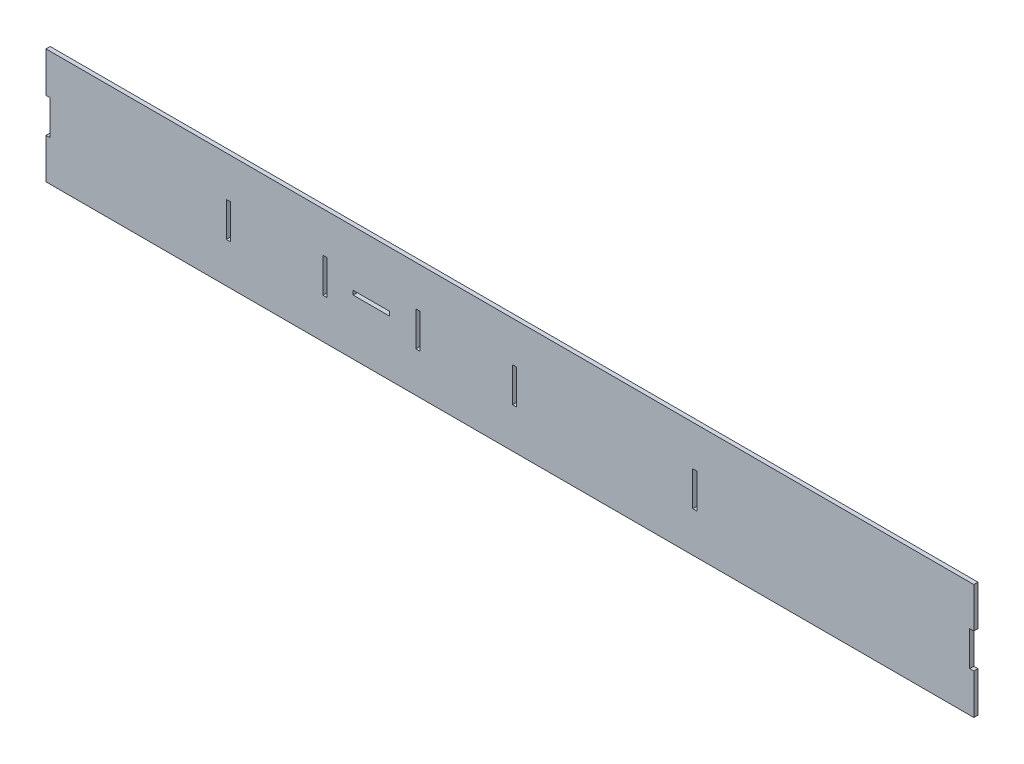
SolidWorks part; units mm, degrees
ref_plane "Front Plane" through (0, 0, 0) normal (0, 0, 1) x (1, 0, 0)
ref_plane "Top Plane" through (0, 0, 0) normal (0, 1, 0) x (1, 0, 0)
ref_plane "Right Plane" through (0, 0, 0) normal (1, 0, 0) x (0, 0, -1)
sketch "Sketch1" plane through (0, 0, 0) normal (0, 0, 1) x (1, 0, 0)
  line L0 (-1.524, -7.869) -> (0, -7.869)
  line L1 (-1.524, -22.6446) -> (338.8496, -22.6446)
  line L2 (-1.524, -22.6446) -> (-1.524, -7.869)
  line L3 (-1.524, 19.6067) -> (338.8496, 19.6067)
  line L4 (338.8496, -22.6446) -> (338.8496, 19.6067)
  line L5 (0, -7.869) -> (0, 4.831)
  line L6 (0, 4.831) -> (-1.524, 4.831)
  line L7 (-1.524, 4.831) -> (-1.524, 19.6067)
  line L9 (101.6, 4.831) -> (100.076, 4.831)
  line L10 (101.6, 4.831) -> (101.6, -7.869)
  line L11 (101.6, -7.869) -> (100.076, -7.869)
  line L12 (100.076, 4.831) -> (100.076, -7.869)
  line L13 (134.1256, -7.869) -> (135.6496, -7.869)
  line L14 (134.1256, -7.869) -> (134.1256, 4.831)
  line L15 (134.1256, 4.831) -> (135.6496, 4.831)
  line L16 (135.6496, -7.869) -> (135.6496, 4.831)
  line L17 (235.7256, -7.869) -> (237.2496, -7.869)
  line L18 (235.7256, -7.869) -> (235.7256, 4.831)
  line L19 (235.7256, 4.831) -> (237.2496, 4.831)
  line L20 (237.2496, -7.869) -> (237.2496, 4.831)
  line L21 (338.8496, -7.869) -> (337.3256, -7.869)
  line L22 (338.8496, -7.869) -> (338.8496, 4.831)
  line L23 (338.8496, 4.831) -> (337.3256, 4.831)
  line L24 (337.3256, -7.869) -> (337.3256, 4.831)
extrude "Boss-Extrude1" add sketch "Sketch1" along normal blind 1.524 contours L21 L24 L23 L4 L3 L7 L6 L5 L0 L2 L1 L12 L9 L10 L11 L16 L13 L14 L15 L20 L17 L18 L19 region at (168.7086, -1.519, 0)
sketch "Sketch2" plane through (0, 0, 1.524) normal (0, 0, 1) x (1, 0, 0)
  line L0 (101.6, -1.519) -> (134.1256, -1.519) construction
  line L1 (66.1281, -7.869) -> (64.6041, -7.869)
  line L2 (66.1281, -7.869) -> (66.1281, 4.831)
  line L3 (66.1281, 4.831) -> (64.6041, 4.831)
  line L4 (64.6041, -7.869) -> (64.6041, 4.831)
  line L5 (101.6, 4.831) -> (101.6, -7.869) construction
  line L6 (134.1256, -7.869) -> (134.1256, 4.831) construction
  line L7 (117.8628, -1.519) -> (117.8628, -74.1573) construction
  line L8 (171.1214, -7.869) -> (171.1214, 4.831)
  line L9 (169.5974, 4.831) -> (171.1214, 4.831)
  line L10 (169.5974, -7.869) -> (169.5974, 4.831)
  line L11 (169.5974, -7.869) -> (171.1214, -7.869)
  line L13 (111.1599, -2.281) -> (124.5657, -2.281)
  line L14 (111.1599, -2.281) -> (111.1599, -0.757)
  line L15 (111.1599, -0.757) -> (124.5657, -0.757)
  line L16 (124.5657, -2.281) -> (124.5657, -0.757)
  line L17 (111.1599, -2.281) -> (124.5657, -0.757) construction
  line L18 (111.1599, -0.757) -> (124.5657, -2.281) construction
  dimension "D1" = 1.524
extrude "Cut-Extrude1" cut sketch "Sketch2" against normal blind 2.54
